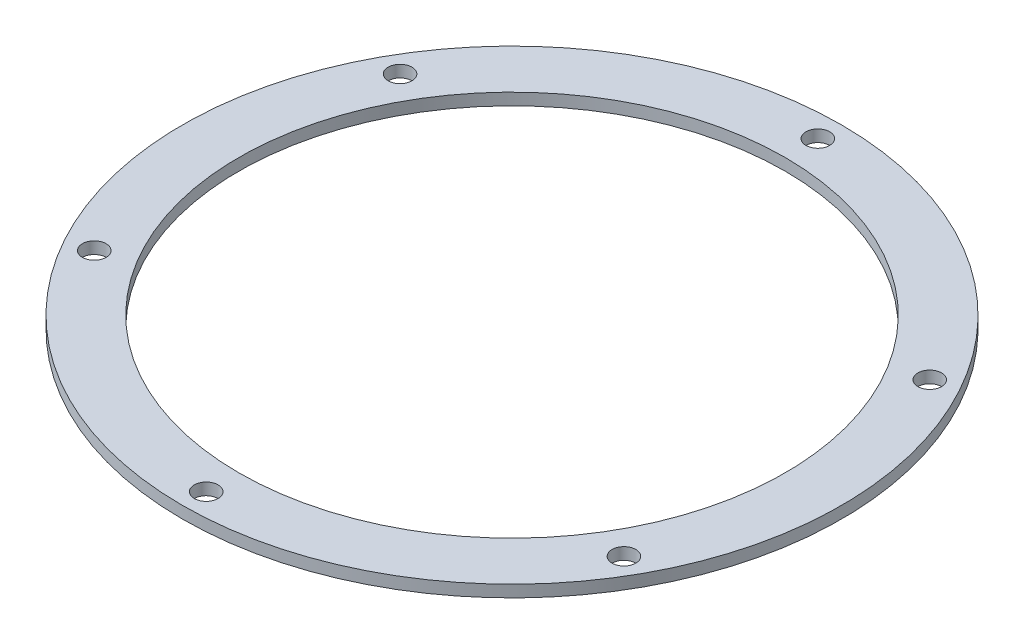
SolidWorks part; units mm, degrees
material "PLA"
ref_plane "Front Plane" through (0, 0, 0) normal (0, 0, 1) x (1, 0, 0)
ref_plane "Top Plane" through (0, 0, 0) normal (0, 1, 0) x (1, 0, 0)
ref_plane "Right Plane" through (0, 0, 0) normal (1, 0, 0) x (0, 0, -1)
sketch "Sketch1" plane through (0, 0, 0) normal (0, 1, 0) x (1, 0, 0)
  circle A0 centre (0, 0) radius 55.5
  circle A1 centre (0, 0) radius 46
  circle A2 centre (0, 0) radius 51.5 construction
  circle A3 centre (0, 51.5) radius 2
  circle A4 centre (44.6003, 25.75) radius 2
  circle A5 centre (44.6003, -25.75) radius 2
  circle A6 centre (0, -51.5) radius 2
  circle A7 centre (-44.6003, -25.75) radius 2
  circle A8 centre (-44.6003, 25.75) radius 2
  point P19 (0, 0)
  dimension "D1" = 111
  dimension "D2" = 92
  dimension "D3" = 103
  dimension "D4" = 4
  dimension "D5" = 6
extrude "Boss-Extrude1" add sketch "Sketch1" along normal blind 2
equation "\"Np_b\" = 55"
equation "\"Np_s\" = 35"
equation "\"Nr_b\" = 190"
equation "\"Nr_s\" = 170"
equation "\"Ns\" = 80"
equation "\"Motor_case_ID\" = 116.8"
equation "\"Motor_case_OD_base_to_chamfer\" = 5"
equation "\"Motor_case_OD_max\" = 131.3"
equation "\"Motor_case_thickness\" = 2.5"
equation "\"air_flow_hole_offset\" = 3"
equation "\"standard_bearing_insertion_chamfer\" = 0.5"
equation "\"alpha_p_b\" = 0.8539582918412449"
equation "\"alpha_p_s\" = 0.8539582918412556"
equation "\"alpha_r_b\" = 0.8539582918412414"
equation "\"alpha_r_s\" = 0.8539582918412307"
equation "\"alpha_s\" = 0.8539582918412272"
equation "\"base_plate_thickness\" = 4"
equation "\"bearing_ID\" = 75"
equation "\"bearing_OD\" = 95"
equation "\"bearing_height\" = 10"
equation "\"bearing mount thickness\" = 8"
equation "\"bearing_retainer_thickness\" = 2"
equation "\"beta_p_b\" = 1.564810689044783"
equation "\"beta_p_s\" = 3.434940559174632"
equation "\"beta_r_b\" = 2.655285004735114"
equation "\"beta_r_s\" = 2.766740113094226"
equation "\"beta_s\" = 0.5420834163175456"
equation "\"carrier_PCD\" = 67.5"
equation "\"carrier_bearing_step_width\" = 1.5"
equation "\"carrier_small_ring_inner_bearing_ID\" = 20"
equation "\"carrier_small_ring_inner_bearing_OD\" = 32"
equation "\"carrier_small_ring_inner_bearing_flap\" = 2"
equation "\"carrier_small_ring_inner_bearing_height\" = 7"
equation "\"carrier_thickness\" = 4"
equation "\"carrier_trapezoidal_support_hole_PCD_offset_bearing_ID\" = 4"
equation "\"carrier_trapezoidal_support_hole_dia\" = 3"
equation "\"carrier_trapezoidal_support_hole_socket_head_dia\" = 5.5"
equation "\"carrier_trapezoidal_support_hole_wrench_size\" = 5.5"
equation "\"carrier_trapezoidal_support_sun_offset\" = 5"
equation "\"case_dist\" = 6.5"
equation "\"case_mounting_PCD\" = 123.8"
equation "\"case_mounting_bolt_depth\" = 4.5"
equation "\"case_mounting_hole_allen_socket_dia\" = 5.5"
equation "\"case_mounting_hole_dia\" = 3"
equation "\"case_mounting_hole_shift\" = 1.0"
equation "\"case_mounting_nut_clearance\" = 2"
equation "\"case_mounting_nut_thickness\" = 2.4"
equation "\"case_mounting_surface_height\" = 4"
equation "\"case_mounting_wrench_size\" = 5.5"
equation "\"central_hole_offset_from_motor_mount_PCD\" = 5"
equation "\"clearance_case_mount_holes_shell_thickness\" = 1"
equation "\"clearance_motor_and_case\" = 5"
equation "\"clearance_planet\" = 1.5"
equation "\"clearance_sun_coupler_sec_carrier\" = 1.5"
equation "\"clr_tip_root\" = 0.125"
equation "\"clr_tip_root_s\" = 0.125"
equation "\"db_p_b\" = 25.84154707161248"
equation "\"db_p_s\" = 16.444620863753396"
equation "\"db_r_b\" = 89.2707989746613"
equation "\"db_r_s\" = 79.87387276680222"
equation "\"db_s\" = 37.58770483143634"
equation "\"dp_p_b\" = 27.5"
equation "\"dp_p_s\" = 17.5"
equation "\"dp_r_b\" = 95.0"
equation "\"dp_r_s\" = 85.0"
equation "\"dp_s\" = 40.0"
equation "\"driver_lower_holes_dist_from_center\" = 13"
equation "\"driver_mount_height\" = 6"
equation "\"driver_mount_holes_dia\" = 3"
equation "\"driver_mount_inserts_OD\" = 4.8"
equation "\"driver_mount_thickness\" = 1.5"
equation "\"driver_side_holes_dist_from_center\" = 22.5"
equation "\"driver_upper_holes_dist_from_center\" = 29"
equation "\"fw_p_b\" = 21.365107882670422"
equation "\"fw_p_s\" = 15.81085678360617"
equation "\"fw_r_b\" = 21.365107882670422"
equation "\"fw_r_s\" = 14.31085678360617"
equation "\"fw_s_calc\" = 4.872946430626146"
equation "\"fw_s_used\" = 44.67596466627659"
equation "\"gear_casing_big_ring_to_bearing_dist\" = 24.81085678360617"
equation "\"gear_casing_thickness\" = 4"
equation "\"h_a\" = 0.5"
equation "\"h_b\" = 0.625"
equation "\"h_f\" = 0.625"
equation "\"module\" = 0.5"
equation "\"motor_OD\" = 106.8"
equation "\"motor_case_OD_base\" = 121.8"
equation "\"motor_height\" = 47.6"
equation "\"motor_mount_hole_PCD\" = 40"
equation "\"motor_mount_hole_dia\" = 5"
equation "\"motor_mount_hole_num\" = 4"
equation "\"motor_output_hole_CSK_OD\" = 8"
equation "\"motor_output_hole_CSK_head_height\" = 2.0"
equation "\"motor_output_hole_PCD\" = 23"
equation "\"motor_output_hole_dia\" = 4"
equation "\"motor_output_hole_num\" = 4"
equation "\"num_planet\" = 5"
equation "\"output_mounting_PCD\" = 103"
equation "\"output_mounting_hole_dia\" = 4"
equation "\"output_mounting_nut_depth\" = 3"
equation "\"output_mounting_nut_thickness\" = 3.2"
equation "\"output_mounting_nut_wrench_size\" = 7"
equation "\"pattern_bulge_dia\" = 3"
equation "\"pattern_depth\" = 2"
equation "\"pattern_num_bulge\" = 18"
equation "\"pattern_offset_from_motor_case_OD_base\" = 3"
equation "\"planet_bearing_OD\" = 12"
equation "\"planet_bearing_width\" = 3.5"
equation "\"planet_bore\" = 10"
equation "\"planet_pin_bolt_dia\" = 5"
equation "\"planet_pin_bolt_wrench_size\" = 8"
equation "\"planet_pin_socket_head_dia\" = 8.5"
equation "\"planet_shaft_dia\" = 8"
equation "\"planet_shaft_step_offset\" = 1"
equation "\"pressure_angle\" = 20.0"
equation "\"pressure angle\" = 20.0"
equation "\"ring_OD_b\" = 105.0"
equation "\"ring_radial_thickness\" = 5"
equation "\"ring_to_chamfer_clearance\" = 1.5"
equation "\"sec_carrier_thickness\" = 5"
equation "\"small_ring_case_thickness\" = 4"
equation "\"small_ring_output_wall_thickness\" = 5"
equation "\"small_ring_output_wall_to_bearing_shaft_attachement_hole_CSK_OD\" = 8"
equation "\"small_ring_output_wall_to_bearing_shaft_attachement_hole_CSK_head_height\" = 2.0"
equation "\"small_ring_output_wall_to_bearing_shaft_attachement_hole_depth\" = 6.5"
equation "\"small_ring_output_wall_to_bearing_shaft_attachement_hole_dia\" = 4"
equation "\"small_ring_output_wall_to_bearing_shaft_attachement_hole_num\" = 3"
equation "\"small_ring_output_wall_to_bearing_shaft_attachement_hole_pcd\" = 12"
equation "\"small_ring_output_wall_to_bearing_shaft_attachement_nut_thickness\" = 3.2"
equation "\"small_ring_output_wall_to_bearing_shaft_attachement_nut_wrench\" = 7"
equation "\"standard_clearance_1_5mm\" = 1.5"
equation "\"standard_fillet_1_5mm\" = 1.5"
equation "\"sun_central_bolt_dia\" = 5"
equation "\"sun_central_bolt_socket_head_dia\" = 8.5"
equation "\"sun_coupler_hub_thickness\" = 4"
equation "\"sun_hub_dia\" = 30.0"
equation "\"sun_shaft_bearing_ID\" = 8"
equation "\"sun_shaft_bearing_OD\" = 16"
equation "\"sun_shaft_bearing_width\" = 5"
equation "\"wire_slot_dist_from_center\" = 45.5"
equation "\"wire_slot_length\" = 10"
equation "\"wire_slot_radius\" = 3"
equation "\"tight_clearance_3DP\" = 0.4"
equation "\"loose_clearance_3DP\" = 0.8"
equation "\"D1@Sketch1\"= \"bearing_OD\" + \"bearing mount thickness\" * 2"
equation "\"D2@Sketch1\"=\"bearing_OD\" -  \"standard_clearance_1_5mm\"*2"
equation "\"D3@Sketch1\"= \"output_mounting_PCD\""
equation "\"D4@Sketch1\"= \"output_mounting_hole_dia\""
equation "\"D1@Boss-Extrude1\"= \"bearing_retainer_thickness\""
